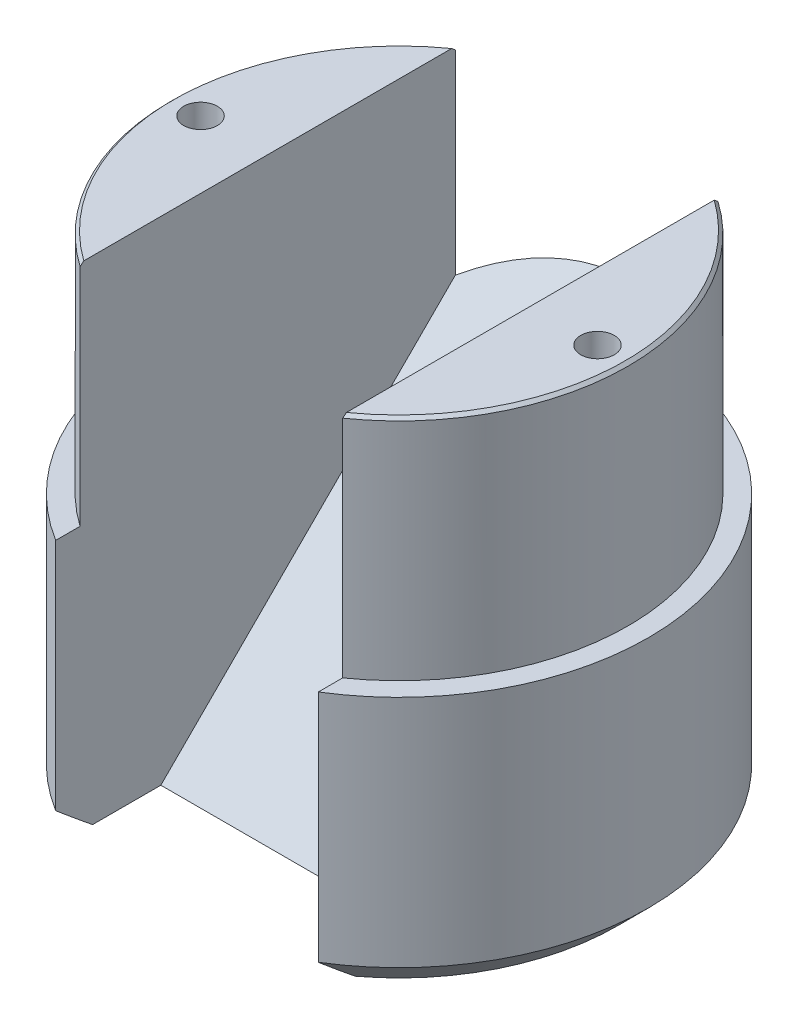
SolidWorks part; units mm, degrees
material "Alliage 1060"
ref_plane "Plan de face" through (0, 0, 0) normal (0, 0, 1) x (1, 0, 0)
ref_plane "Plan de dessus" through (0, 0, 0) normal (0, 1, 0) x (1, 0, 0)
ref_plane "Plan de droite" through (0, 0, 0) normal (1, 0, 0) x (0, 0, -1)
sketch "Esquisse1" plane through (0, 0, 0) normal (0, 0, 1) x (1, 0, 0)
  line L0 (0, 89.9345) -> (0, -51.3299) construction
  line L1 (0, -23) -> (21.5, -23)
  line L2 (0, -23) -> (0, 25.4)
  line L3 (0, 25.4) -> (22.2, 25.4)
  line L4 (24.5, -20) -> (24.5, 3)
  line L5 (24.5, 3) -> (22.5, 3)
  line L6 (22.5, 3) -> (22.5, 25.1)
  line L9 (22.5, 25.6) -> (-22.5, 25.6) construction
  line L10 (126.8216, -25) -> (-126.8216, -25) construction
  line L13 (21.5, -23) -> (24.5, -20)
  line L16 (22.2, 25.4) -> (22.5, 25.1)
  line L18 (22.5, 3.1) -> (22.5, 9.9) construction
  line L19 (-22.6, 3) -> (22.6, 3) construction
  point P18 (24.5, -23)
  point P20 (22.5, 25.4)
  dimension "D1" = 2
  dimension "D2" = 0.2
  dimension "D3" = 2
  dimension "D6" = 3
  dimension "D7" = 0.3
revolve "Révolution1" add sketch "Esquisse1" angle 360 about L0
sketch "Esquisse2" plane through (0, 0, 0) normal (1, 0, 0) x (0, 0, -1)
  line L0 (-24.5, -37) -> (24.5, 12)
  line L1 (24.5, 12) -> (24.5, 25.4)
  line L2 (0, -25) -> (0, 0) construction
  line L3 (24.5, 25.4) -> (-24.5, 25.4)
  line L4 (126.8216, 0) -> (-126.8216, 0) construction
  line L5 (-24.5, 25.4) -> (-24.5, -37)
  line L7 (126.8216, -25) -> (-126.8216, -25) construction
  line L8 (24.5, -20) -> (24.5, 3) construction
  line L9 (-24.5, 3) -> (-24.5, -20) construction
  line L10 (22.5, 25.4) -> (-22.5, 25.4) construction
  point P17 (0, -12.5)
  dimension "D1" = 45
extrude "Enlèv. mat.-Extru.1" cut sketch "Esquisse2" against normal blind 12.9 and the other way blind 12.9
hole_wizard "Trou taraudé M4x0.71" positions "Esquisse6" profile "Esquisse5" tap size "M4x0.7" standard "ISO"
sketch "Esquisse6" plane through (0, 25.4, 0) normal (0, 1, 0) x (-1, 0, 0)
  line L0 (-19.5, 0) -> (19.5, 0) construction
  arc A0 (-12.9, 18.4347) -> (-12.9, -18.4347) centre (0, 0) ccw construction
  point P0 (-19.5, 0)
  point P1 (19.5, 0)
  dimension "D1" = 3
sketch "Esquisse5" plane through (19.5, 25.4, 0) normal (1, 0, 0) x (0, 0, 1)
  line L0 (0, 0) -> (0, 10.9914)
  line L1 (0, 10.9914) -> (1.65, 10)
  line L2 (1.65, 10) -> (1.65, 0)
  line L5 (1.65, 0) -> (0, 0)
  line L10 (0, 10.9914) -> (-1.65, 10) construction
  line L11 (0, -6.35) -> (0, 107.95) construction
  dimension "Diamètre du trou pour taraudage" = 3.3
  dimension "Profondeur du trou pour taraudage" = 10
  dimension "Angle de pointe" = 118
cosmetic thread "Filetage de perçage1" parameters "D1"=10, "D2"=4
cosmetic thread "Filetage de perçage2" parameters "D1"=10, "D2"=4
